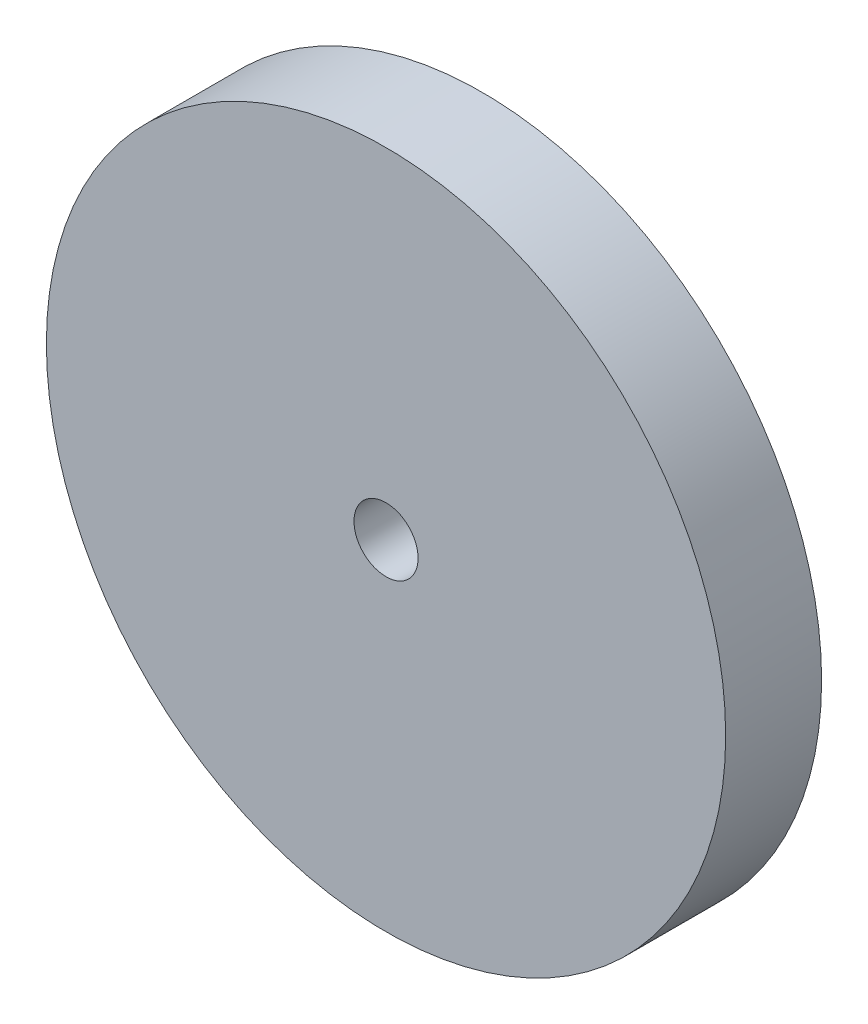
SolidWorks part; units mm, degrees
ref_plane "Front Plane" through (0, 0, 0) normal (0, 0, 1) x (1, 0, 0)
ref_plane "Top Plane" through (0, 0, 0) normal (0, 1, 0) x (1, 0, 0)
ref_plane "Right Plane" through (0, 0, 0) normal (1, 0, 0) x (0, 0, -1)
sketch "Sketch1" plane through (0, 0, 0) normal (0, 0, 1) x (1, 0, 0)
  circle A0 centre (0, 0) radius 19.781
  circle A1 centre (0, 0) radius 1.8669
  dimension "D1" = 39.5619
  dimension "D2" = 3.7338
extrude "Boss-Extrude1" add sketch "Sketch1" along normal blind 5.588
